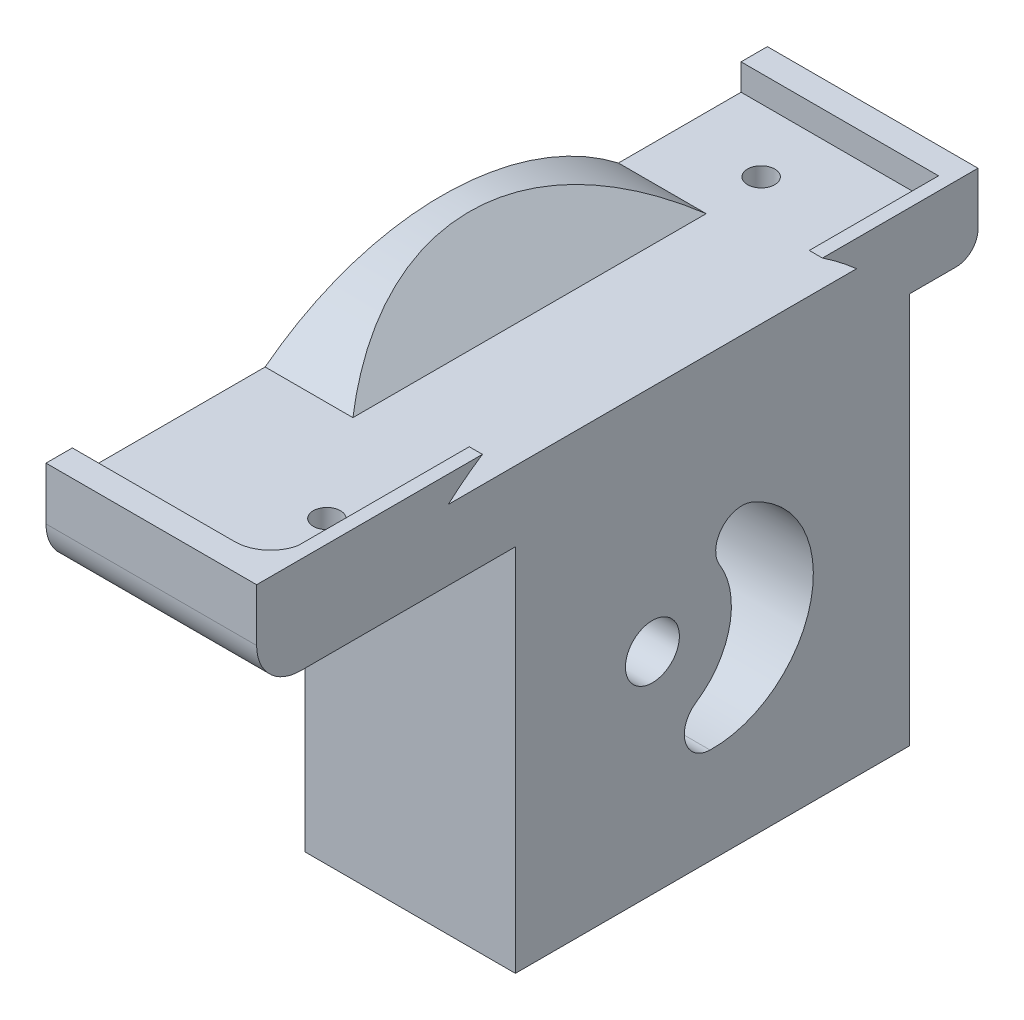
SolidWorks part; units mm, degrees
note: The reader was unsure of these and kept them because the rebuilt part matched: shared geometry of "Sketch1<3>", "Sketch1<4>", "Sketch3<4>", "Sketch3<5>", "Sketch3<6>".
ref_plane "Front Plane" through (0, 0, 0) normal (0, 0, 1) x (1, 0, 0)
ref_plane "Top Plane" through (0, 0, 0) normal (0, 1, 0) x (1, 0, 0)
ref_plane "Right Plane" through (0, 0, 0) normal (1, 0, 0) x (0, 0, -1)
sketch "Sketch1" plane through (170.8655, 0, 0) normal (1, 0, 0) x (0, 0, -1)
  line L0 (-92.1899, 29.7491) -> (-92.1899, -12.3509)
  line L1 (-92.1899, -12.3509) -> (-47.2899, -12.3509)
  line L2 (-47.2899, -12.3509) -> (-47.2899, 32.2491)
  line L3 (-47.2899, 32.2491) -> (-41.9774, 32.2491)
  line L4 (-39.4774, 34.7491) -> (-39.4774, 40.7491)
  line L5 (-39.4774, 40.7491) -> (-42.4774, 40.7491)
  line L6 (-42.4774, 40.7491) -> (-42.4774, 37.7491)
  line L7 (-42.4774, 37.7491) -> (-118.6774, 37.7491)
  line L8 (-118.6774, 37.7491) -> (-118.6774, 40.7491)
  line L9 (-118.6774, 40.7491) -> (-121.6774, 40.7491)
  line L10 (-121.6774, 40.7491) -> (-121.6774, 34.7491)
  line L11 (-116.6774, 29.7491) -> (-92.1899, 29.7491)
  line L12 (6.2857, -12.3509) -> (51.1857, -12.3509) construction
  line L13 (52.5226, 37.7491) -> (-12.6774, 37.7491) construction
  line L14 (-27.5774, 17.4555) -> (-27.5774, 14.4555) construction
  line L15 (-42.5774, 37.7491) -> (-42.5774, 47.0248) construction
  line L16 (-12.5774, 47.0248) -> (-12.5774, 37.7491) construction
  line L17 (-12.6774, 37.7491) -> (-12.6774, 40.7491) construction
  line L18 (-15.6774, 40.7491) -> (-15.6774, 34.7491) construction
  line L20 (-10.6774, 29.7491) -> (6.2857, 29.7491) construction
  line L21 (-80.5774, 103.2788) -> (-80.5774, -64.2701) construction
  line L22 (-118.5774, 37.7491) -> (-118.5774, 40.7491) construction
  line L23 (55.5226, 40.7491) -> (52.5226, 40.7491) construction
  circle A0 centre (-76.5774, 11.5987) radius 3.075
  circle A1 centre (-76.5774, 11.5987) radius 6.11
  circle A2 centre (21.8982, 11.5987) radius 3.075 construction
  circle A3 centre (21.8982, 11.5987) radius 6.11 construction
  circle A4 centre (-69.7399, 10.0991) radius 22.45
  circle A5 centre (28.7357, 10.0991) radius 22.45 construction
  arc A6 (-41.9774, 32.2491) -> (-39.4774, 34.7491) centre (-41.9774, 34.7491) ccw
  arc A7 (-121.6774, 34.7491) -> (-116.6774, 29.7491) centre (-116.6774, 34.7491) ccw
  circle A8 centre (-69.7399, 10.0991) radius 18.45 construction
  arc A9 (53.0226, 32.7491) -> (55.5226, 35.2491) centre (53.0226, 35.2491) ccw construction
  arc A10 (-15.6774, 34.7491) -> (-10.6774, 29.7491) centre (-10.6774, 34.7491) ccw construction
  circle A11 centre (-69.7399, 10.0991) radius 18.55
  circle A13 centre (28.7357, 10.0991) radius 18.45 construction
  circle M20 centre (-76.5774, 11.5987) radius 5.25
  dimension "D1" = 0.1
extrude "Boss-Extrude1" add sketch "Sketch1" along normal up to surface (5.5 mm away) contours A4 L0 L1 | L10 A7 L11 L0 A4 L2 L3 A6 L4 L5 L6 L7 L8 L9 | A4 L1 L2 | A4 A1 | A0 M20 | A1 M20 | A11 A1
extrude "Boss-Extrude2" add sketch "Sketch1<3>" against normal up to surface (6 mm away) contours A4 L0 L1 | A4 L1 L2 | L10 A7 L11 L0 A4 L2 L3 A6 L4 L5 L6 L7 L8 L9 | A4 A1 | A11 A1
sketch "Sketch1<3>" plane through (170.8655, 0, 0) normal (1, 0, 0) x (0, 0, -1) same geometry as "Sketch1"
extrude "Boss-Extrude3" add sketch "Sketch1<4>" along normal up to surface (11 mm away) from surface contours A4 L0 L1 | A4 L1 L2 | L10 A7 L11 L0 A4 L2 L3 A6 L4 L5 L6 L7 L8 L9 | A4 A1
sketch "Sketch1<4>" plane through (170.8655, 0, 0) normal (1, 0, 0) x (0, 0, -1) same geometry as "Sketch1"
sketch "Sketch2" plane through (153.8655, 0, 0) normal (-1, 0, 0) x (0, 0, 1)
  line L0 (118.6774, 37.7491) -> (42.4774, 37.7491) construction
  line L1 (56.4489, 37.7491) -> (96.7059, 37.7491)
  line L2 (-1.2941, 37.7491) -> (-41.5511, 37.7491) construction
  arc A0 (56.4489, 37.7491) -> (96.7059, 37.7491) centre (76.5774, 11.5987) cw
  arc A1 (-1.2941, 37.7491) -> (-41.5511, 37.7491) centre (-21.4226, 11.5987) ccw construction
  arc A2 (99.8401, 37.7491) -> (53.3147, 37.7491) centre (76.5774, 11.5987) ccw construction
extrude "Boss-Extrude4" add sketch "Sketch2" against normal up to vertex (10 mm away)
draft "Draft1" type of draft neutral plane draft angle 45 faces to draft 1 face at (163.8655, 41.1739, 76.5774) neutral plane through (274.2248, 37.7491, 0) neutral plane normal (0, 1, 0) parameters "D1"=45
sketch "Sketch3" plane through (0, 37.7491, 0) normal (0, 1, 0) x (1, 0, 0)
  line L1 (163.3655, -46.3929) -> (160.5155, -48.0384)
  line L2 (160.5155, -48.0384) -> (160.5155, -51.3293)
  line L3 (160.5155, -51.3293) -> (163.3655, -52.9747)
  line L4 (163.3655, -52.9747) -> (166.2155, -51.3293)
  line L5 (166.2155, -51.3293) -> (166.2155, -48.0384)
  line L6 (166.2155, -48.0384) -> (163.3655, -46.3929)
  line L7 (175.6314, -108.145) -> (173.9859, -105.295)
  line L8 (173.9859, -105.295) -> (170.695, -105.295)
  line L9 (170.695, -105.295) -> (169.0496, -108.145)
  line L10 (169.0496, -108.145) -> (170.695, -110.995)
  line L11 (170.695, -110.995) -> (173.9859, -110.995)
  line L12 (173.9859, -110.995) -> (175.6314, -108.145)
  line L13 (167.2246, 46.1772) -> (170.0746, 44.5317) construction
  line L14 (160.5155, -48.0384) -> (160.5155, -47.2899)
  line L15 (160.5155, -47.2899) -> (166.2155, -47.2899)
  line L16 (166.2155, -47.2899) -> (166.2155, -48.0384)
  line L17 (176.3655, -47.2899) -> (153.8655, -47.2899) construction
  line L18 (176.3655, -118.6774) -> (153.8655, -118.6774) construction
  line L19 (176.3655, -42.4774) -> (176.3655, -118.6774) construction
  line L20 (176.3655, -118.6774) -> (153.8655, -118.6774) construction
  circle A0 centre (163.3655, -49.6838) radius 2.85 construction
  circle A1 centre (172.3405, -108.145) radius 2.85 construction
  arc A2 (176.3655, -115.4774) -> (172.3655, -118.6774) centre (172.3655, -114.5774) cw
  circle A3 centre (163.3655, -49.6838) radius 1.55
  circle A4 centre (172.3405, -108.145) radius 1.55
  arc A5 (172.3655, -118.5774) -> (176.3655, -114.5774) centre (172.3655, -114.5774) ccw construction
  circle A6 centre (163.3655, -49.6838) radius 1.55 construction
  circle A7 centre (172.3405, -108.145) radius 1.55 construction
  line M14 (153.8655, -118.6774) -> (176.3655, -118.6774)
  line M15 (176.3655, -118.6774) -> (176.3655, -42.4774)
extrude "Boss-Extrude5" add sketch "Sketch3" along normal up to surface (3 mm away) contours A2 M15 M14 up to face at (165.1155, 40.7491, 120.1774)
sketch "Sketch4" plane through (176.3655, 0, 0) normal (1, 0, 0) x (0, 0, -1)
  line L0 (-115.4774, 40.7491) -> (-95.9488, 40.7491)
  line L2 (-42.4774, 40.7491) -> (-57.206, 40.7491)
  line L4 (-90.6774, 40.7491) -> (-53.7903, 40.7491) construction
  line L5 (-114.5774, 40.7491) -> (-99.3645, 40.7491) construction
  line L6 (-42.4774, 37.7491) -> (-115.4774, 37.7491) construction
  line L12 (-42.4774, 37.7491) -> (-115.4774, 37.7491)
  line L13 (-115.4774, 37.7491) -> (-115.4774, 40.7491)
  line L14 (-115.4774, 40.7491) -> (-121.6774, 40.7491)
  line L15 (-121.6774, 40.7491) -> (-121.6774, 34.7491)
  line L16 (-116.6774, 29.7491) -> (-92.1899, 29.7491)
  line L17 (-92.1899, 29.7491) -> (-92.1899, -12.3509)
  line L18 (-92.1899, -12.3509) -> (-47.2899, -12.3509)
  line L19 (-47.2899, -12.3509) -> (-47.2899, 32.2491)
  line L20 (-47.2899, 32.2491) -> (-41.9774, 32.2491)
  line L21 (-39.4774, 34.7491) -> (-39.4774, 40.7491)
  line L22 (-39.4774, 40.7491) -> (-42.4774, 40.7491)
  line L23 (-42.4774, 40.7491) -> (-42.4774, 37.7491)
  line L24 (-42.4774, 37.7491) -> (-115.4774, 37.7491)
  line L25 (-115.4774, 37.7491) -> (-115.4774, 40.7491)
  line L26 (-115.4774, 40.7491) -> (-121.6774, 40.7491)
  line L27 (-121.6774, 40.7491) -> (-121.6774, 34.7491)
  line L28 (-116.6774, 29.7491) -> (-92.1899, 29.7491)
  line L29 (-92.1899, 29.7491) -> (-92.1899, -12.3509)
  line L30 (-92.1899, -12.3509) -> (-47.2899, -12.3509)
  line L31 (-47.2899, -12.3509) -> (-47.2899, 32.2491)
  line L32 (-47.2899, 32.2491) -> (-41.9774, 32.2491)
  line L33 (-39.4774, 34.7491) -> (-39.4774, 40.7491)
  line L34 (-39.4774, 40.7491) -> (-42.4774, 40.7491)
  line L35 (-42.4774, 40.7491) -> (-42.4774, 37.7491)
  arc A0 (-99.8401, 37.7491) -> (-95.9488, 40.7491) centre (-76.5774, 11.5987) cw
  arc A1 (-57.206, 40.7491) -> (-53.3147, 37.7491) centre (-76.5774, 11.5987) cw
  arc A2 (-121.6774, 34.7491) -> (-116.6774, 29.7491) centre (-116.6774, 34.7491) ccw
  arc A3 (-41.9774, 32.2491) -> (-39.4774, 34.7491) centre (-41.9774, 34.7491) ccw
  arc A4 (-121.6774, 34.7491) -> (-116.6774, 29.7491) centre (-116.6774, 34.7491) ccw
  arc A5 (-41.9774, 32.2491) -> (-39.4774, 34.7491) centre (-41.9774, 34.7491) ccw
  arc A6 (-53.3147, 37.7491) -> (-99.8401, 37.7491) centre (-76.5774, 11.5987) ccw construction
  line M17 (-42.4774, 37.7491) -> (-115.4774, 37.7491)
  line M18 (-115.4774, 37.7491) -> (-115.4774, 40.7491)
  line M19 (-115.4774, 40.7491) -> (-121.6774, 40.7491)
  line M20 (-121.6774, 40.7491) -> (-121.6774, 34.7491)
  arc M21 (-121.6774, 34.7491) -> (-116.6774, 29.7491) centre (-116.6774, 34.7491) ccw
  line M22 (-116.6774, 29.7491) -> (-92.1899, 29.7491)
  line M23 (-92.1899, 29.7491) -> (-92.1899, -12.3509)
  line M24 (-92.1899, -12.3509) -> (-47.2899, -12.3509)
  line M25 (-47.2899, -12.3509) -> (-47.2899, 32.2491)
  line M26 (-47.2899, 32.2491) -> (-41.9774, 32.2491)
  arc M27 (-41.9774, 32.2491) -> (-39.4774, 34.7491) centre (-41.9774, 34.7491) ccw
  line M28 (-39.4774, 34.7491) -> (-39.4774, 40.7491)
  line M29 (-39.4774, 40.7491) -> (-42.4774, 40.7491)
  line M30 (-42.4774, 40.7491) -> (-42.4774, 37.7491)
  circle M31 centre (-76.5774, 11.5987) radius 3.075
  dimension "D1" = 0
extrude "Boss-Extrude6" add sketch "Sketch4" along normal up to surface (1.5 mm away) contours L24 M30 M17 M18 M19 M20 M21 M22 M23 M24 M25 M26 M27 M28 M29 M31 | L24 A0 L0 M18 | L2 A1 M17 M30
extrude "Cut-Extrude1" cut sketch "Sketch3<4>" against normal up to surface (11 mm away) contours A4 | A3
sketch "Sketch3<4>" plane through (0, 37.7491, 0) normal (0, 1, 0) x (1, 0, 0) same geometry as "Sketch3"
extrude "Cut-Extrude2" cut sketch "Sketch3<5>" along normal up to surface (2.6 mm away) from surface contours L15 L1 L2 L3 L4 L5 L6 A3 | L16 L15 L6 | L15 L14 L1
sketch "Sketch3<5>" plane through (0, 37.7491, 0) normal (0, 1, 0) x (1, 0, 0) same geometry as "Sketch3"
extrude "Cut-Extrude3" cut sketch "Sketch3<6>" along normal up to surface (2.5 mm away) from surface at -8 contours L11 L12 L7 L8 L9 L10 A4 starting at face at (170.7905, 29.7491, 108.145)
sketch "Sketch3<6>" plane through (0, 37.7491, 0) normal (0, 1, 0) x (1, 0, 0) same geometry as "Sketch3"
sketch "Sketch5" plane through (177.8655, 0, 0) normal (1, 0, 0) x (0, 0, -1)
  arc A1 (-65.1743, 20.654) -> (-70.0106, -1.3977) centre (-69.7399, 10.0991) cw
  arc A2 (-68.9183, 16.3251) -> (-71.5993, 4.1008) centre (-76.5774, 11.5987) cw
  arc A3 (-65.1743, 20.654) -> (-68.9183, 16.3251) centre (-66.3653, 17.9005) ccw
  arc A4 (-71.5993, 4.1008) -> (-70.0106, -1.3977) centre (-69.94, 1.6015) ccw
  arc A5 (33.3013, 20.654) -> (29.5573, 16.3251) centre (32.1103, 17.9005) ccw construction
  arc A6 (26.8763, 4.1008) -> (28.4651, -1.3977) centre (28.5357, 1.6015) ccw construction
  arc A7 (28.4651, -1.3977) -> (33.3013, 20.654) centre (28.7357, 10.0991) ccw construction
  arc A8 (26.8763, 4.1008) -> (29.5573, 16.3251) centre (21.8982, 11.5987) ccw construction
  circle A9 centre (-69.7399, 10.0991) radius 18.55 construction
  circle A10 centre (-76.5774, 11.5987) radius 6.11 construction
extrude "Cut-Extrude4" cut sketch "Sketch5" against normal up to surface (13 mm away) up to face at (164.8655, 11.5987, 70.4674)
